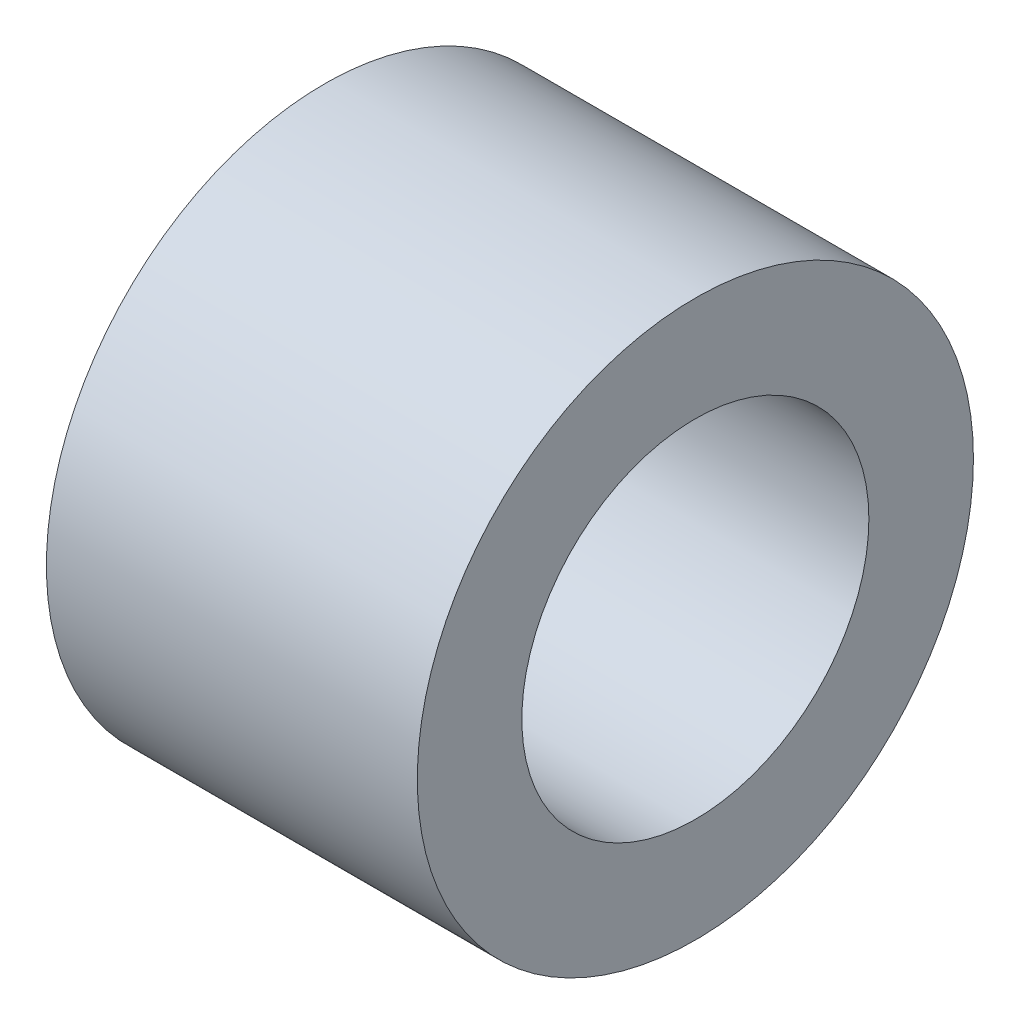
SolidWorks part; units mm, degrees
material "PET"
ref_plane "Front Plane" through (0, 0, 0) normal (0, 0, 1) x (1, 0, 0)
ref_plane "Top Plane" through (0, 0, 0) normal (0, 1, 0) x (1, 0, 0)
ref_plane "Right Plane" through (0, 0, 0) normal (1, 0, 0) x (0, 0, -1)
sketch "Sketch1" plane through (0, 0, 0) normal (1, 0, 0) x (0, 0, -1)
  circle A0 centre (0, 0) radius 7.9375
  circle A1 centre (0, 0) radius 4.953
  dimension "D1" = 9.906
  dimension "D2" = 15.875
extrude "Boss-Extrude1" add sketch "Sketch1" along normal blind 10.5875
